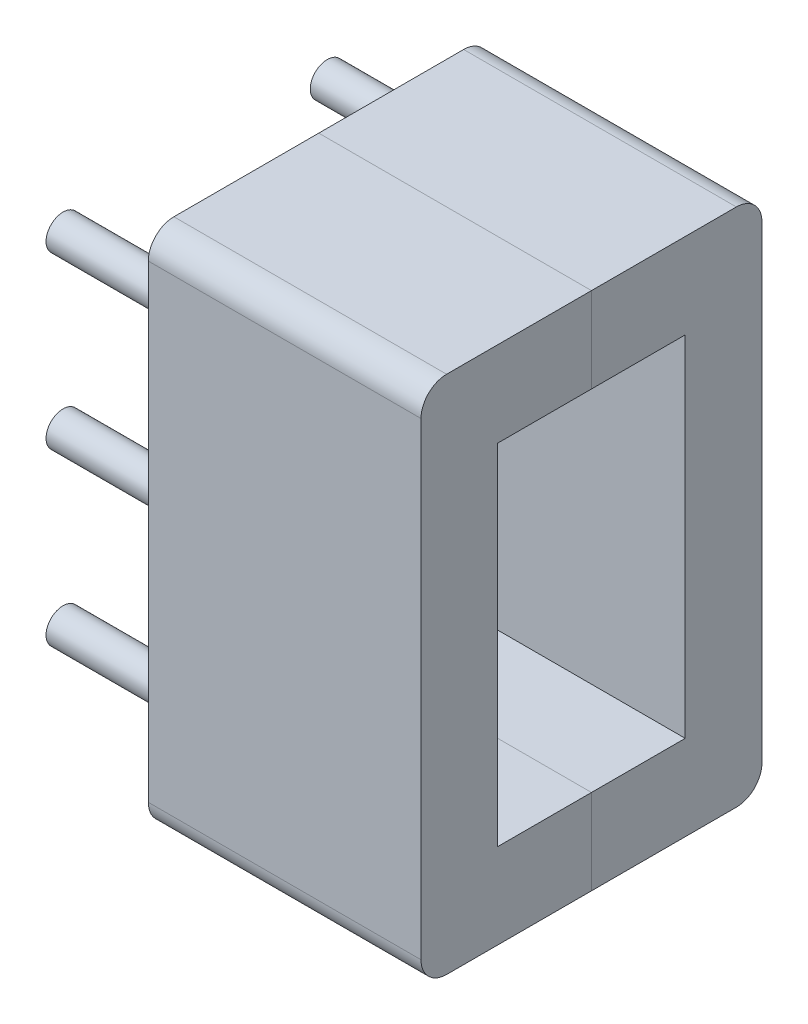
SolidWorks part; units mm, degrees
ref_plane "Alzado" through (0, 0, 0) normal (0, 0, 1) x (1, 0, 0)
ref_plane "Planta" through (0, 0, 0) normal (0, 1, 0) x (1, 0, 0)
ref_plane "Vista lateral" through (0, 0, 0) normal (1, 0, 0) x (0, 0, -1)
sketch "Croquis2" plane through (0, 0, 0) normal (1, 0, 0) x (0, 0, -1)
  line L0 (0, 24.489) -> (0, -53.3578) construction
  line L1 (5.835, 13.2874) -> (5.835, 12.9749) construction
  line L2 (10, 6.2874) -> (10, 3.7874) construction
  line L3 (5.835, -38.7126) -> (5.835, -38.4002) construction
  line L4 (5.835, -38.7126) -> (8, -38.7126) construction
  line L5 (9, -32.7126) -> (9, -37.7126) construction
  line L6 (10, -29.2126) -> (10, -31.7126) construction
  line L7 (5.835, 13.2874) -> (8, 13.2874) construction
  line L8 (9, 7.2874) -> (9, 12.2874) construction
  line L9 (6.5, 7.2874) -> (-6.5, 7.2874) construction
  line L10 (10, -29.2126) -> (10, 3.7874) construction
  line L11 (5.835, 13.2874) -> (5.835, 12.9749) construction
  line L12 (10, 6.2874) -> (10, 3.7874) construction
  line L13 (5.835, -38.7126) -> (5.835, -38.4002) construction
  line L14 (5.835, -38.7126) -> (8, -38.7126) construction
  line L15 (9, -32.7126) -> (9, -37.7126) construction
  line L16 (10, -29.2126) -> (10, -31.7126) construction
  line L17 (5.835, 13.2874) -> (8, 13.2874) construction
  line L18 (9, 7.2874) -> (9, 12.2874) construction
  line L19 (6.5, 7.2874) -> (-6.5, 7.2874) construction
  line L20 (10, -29.2126) -> (10, 3.7874) construction
  line L21 (-20, 17.7874) -> (20, 17.7874)
  line L22 (20, 17.7874) -> (20, -43.2126)
  line L24 (20, -43.2126) -> (-20, -43.2126)
  line L25 (-20, 17.7874) -> (-20, -43.2126)
  line L26 (-6.5, -32.7126) -> (6.5, -32.7126) construction
  line L27 (9, -32.7126) -> (6.5, -32.7126) construction
  line L28 (-6.5, -32.7126) -> (6.5, -32.7126) construction
  line L29 (9, -32.7126) -> (6.5, -32.7126) construction
  line L30 (-3, -33.7126) -> (-3, -32.7126) construction
  line L31 (3, -33.7126) -> (3, -32.7126) construction
  line L32 (-3, -33.7126) -> (-3, -32.7126) construction
  line L33 (3, -33.7126) -> (3, -32.7126) construction
  arc A0 (5.835, -38.4002) -> (4.335, -38.4002) centre (5.085, -36.3426) ccw construction
  arc A1 (4.335, 12.9749) -> (5.835, 12.9749) centre (5.085, 10.9174) ccw construction
  arc A2 (5.835, -38.4002) -> (4.335, -38.4002) centre (5.085, -36.3426) ccw construction
  arc A3 (4.335, 12.9749) -> (5.835, 12.9749) centre (5.085, 10.9174) ccw construction
  arc A4 (8, -38.7126) -> (9, -37.7126) centre (8, -37.7126) ccw construction
  arc A5 (9, -32.7126) -> (10, -31.7126) centre (9, -31.7126) ccw construction
  arc A6 (9, 12.2874) -> (8, 13.2874) centre (8, 12.2874) ccw construction
  arc A7 (10, 6.2874) -> (9, 7.2874) centre (9, 6.2874) ccw construction
  arc A8 (8, -38.7126) -> (9, -37.7126) centre (8, -37.7126) ccw construction
  arc A9 (9, -32.7126) -> (10, -31.7126) centre (9, -31.7126) ccw construction
  arc A10 (9, 12.2874) -> (8, 13.2874) centre (8, 12.2874) ccw construction
  arc A11 (10, 6.2874) -> (9, 7.2874) centre (9, 6.2874) ccw construction
  point P31 (0, -43.2126)
  point P33 (0, 17.7874)
  dimension "D1" = 4.5
  dimension "D2" = 10
  dimension "D3" = 4.5
extrude "Saliente-Extruir1" add sketch "Croquis2" against normal blind 32
sketch "Croquis4" plane through (0, 0, 0) normal (1, 0, 0) x (0, 0, -1)
  line L0 (3, -33.7126) -> (3, -32.7126) construction
  line L1 (-6.5, -32.7126) -> (6.5, -32.7126) construction
  line L2 (9, -32.7126) -> (6.5, -32.7126) construction
  line L3 (10, -29.2126) -> (10, -31.7126) construction
  line L4 (10, 6.2874) -> (10, 3.7874) construction
  line L5 (10, -29.2126) -> (10, 3.7874) construction
  line L6 (6.5, 7.2874) -> (-6.5, 7.2874) construction
  line L7 (0, 24.489) -> (0, -53.3578) construction
  line L8 (3, -33.7126) -> (3, -32.7126) construction
  line L9 (-6.5, -32.7126) -> (6.5, -32.7126) construction
  line L10 (9, -32.7126) -> (6.5, -32.7126) construction
  line L11 (10, -29.2126) -> (10, -31.7126) construction
  line L12 (10, 6.2874) -> (10, 3.7874) construction
  line L13 (10, -29.2126) -> (10, 3.7874) construction
  line L14 (6.5, 7.2874) -> (-6.5, 7.2874) construction
  line L15 (0, 24.489) -> (0, -53.3578) construction
  line L16 (-11, 7.7874) -> (11, 7.7874)
  line L17 (11, 7.7874) -> (11, -33.2126)
  line L19 (-11, 7.7874) -> (-11, -33.2126)
  line L35 (3, -33.7126) -> (2.5, -34.2126) construction
  line L43 (11, -33.2126) -> (-11, -33.2126)
  arc A0 (9, -32.7126) -> (10, -31.7126) centre (9, -31.7126) ccw construction
  arc A1 (9, -32.7126) -> (10, -31.7126) centre (9, -31.7126) ccw construction
  point P14 (0, -33.2126)
  point P20 (0, 7.7874)
  point P22 (0, -43.2126)
  dimension "D1" = 0.5
  dimension "D2" = 1
  dimension "D3" = 0.5
  dimension "D8" = 0.5
  dimension "D9" = 2.5
extrude "Cortar-Extruir1" cut sketch "Croquis4" against normal through all both and the other way through all
sketch "Croquis5" plane through (-32, 0, 0) normal (-1, 0, 0) x (0, 0, 1)
  line L0 (-9, 7.2874) -> (-9, 12.2874) construction
  line L1 (-9, -32.7126) -> (-9, -37.7126) construction
  line L2 (-5.835, -38.7126) -> (-8, -38.7126) construction
  line L3 (-5.835, 13.2874) -> (-8, 13.2874) construction
  line L4 (-9, 7.2874) -> (-9, 12.2874) construction
  line L5 (-9, -32.7126) -> (-9, -37.7126) construction
  line L6 (-5.835, -38.7126) -> (-8, -38.7126) construction
  line L7 (-5.835, 13.2874) -> (-8, 13.2874) construction
  line L8 (0, 24.489) -> (0, -53.3578) construction
  line L9 (0, 24.489) -> (0, -53.3578) construction
  line L10 (9.5, 13.7874) -> (-9.5, 13.7874)
  line L11 (-9.5, 13.7874) -> (-9.5, -39.2126)
  line L12 (-9.5, -39.2126) -> (9.5, -39.2126)
  line L13 (9.5, 13.7874) -> (9.5, -39.2126)
  arc A0 (-4.335, -38.4002) -> (-5.835, -38.4002) centre (-5.085, -36.3426) ccw construction
  arc A1 (-5.835, 12.9749) -> (-4.335, 12.9749) centre (-5.085, 10.9174) ccw construction
  arc A2 (-4.335, -38.4002) -> (-5.835, -38.4002) centre (-5.085, -36.3426) ccw construction
  arc A3 (-5.835, 12.9749) -> (-4.335, 12.9749) centre (-5.085, 10.9174) ccw construction
  point P21 (0, -39.2126)
  point P22 (0, 13.7874)
  dimension "D1" = 0.5
  dimension "D2" = 0.5
  dimension "D3" = 0.5
extrude "Cortar-Extruir2" cut sketch "Croquis5" against normal blind 8 and the other way through all
sketch "Croquis7" plane through (-24, 0, 0) normal (-1, 0, 0) x (0, 0, 1)
  line L4 (-9.5, 7.7874) -> (9.5, 7.7874)
  line L5 (9.5, 7.7874) -> (9.5, 13.7874)
  line L6 (9.5, 13.7874) -> (-9.5, 13.7874)
  line L7 (-9.5, 13.7874) -> (-9.5, 7.7874)
  line L8 (-9.5, 7.7874) -> (9.5, 7.7874)
  line L9 (9.5, 7.7874) -> (9.5, 13.7874)
  line L10 (9.5, 13.7874) -> (-9.5, 13.7874)
  line L11 (-9.5, 13.7874) -> (-9.5, 7.7874)
  line L12 (9.5, -33.2126) -> (-9.5, -33.2126)
  line L13 (-9.5, -33.2126) -> (-9.5, -39.2126)
  line L14 (-9.5, -39.2126) -> (9.5, -39.2126)
  line L15 (9.5, -39.2126) -> (9.5, -33.2126)
  line L16 (9.5, -33.2126) -> (-9.5, -33.2126)
  line L17 (-9.5, -33.2126) -> (-9.5, -39.2126)
  line L18 (-9.5, -39.2126) -> (9.5, -39.2126)
  line L19 (9.5, -39.2126) -> (9.5, -33.2126)
  dimension "D1" = 0
  dimension "D2" = 0
extrude "Saliente-Extruir2" add sketch "Croquis7" along normal up to surface (8 mm away) from offset 2.5 up to face at (-32, -12.7126, 0)
sketch "Croquis9" plane through (-32, 0, 0) normal (1, 0, 0) x (0, 0, -1)
  line L0 (-15.5, 3.7699) -> (-15.5, -40.0796) construction
  line L2 (100, 3.7699) -> (-100, 3.7699) construction
  line L3 (100, 12.7699) -> (-100, 12.7699) construction
  line L4 (-20, 17.7874) -> (-20, -43.2126) construction
  line L5 (-11, -33.2126) -> (-11, 7.7874) construction
  line L6 (-20, 17.7874) -> (-20, -43.2126) construction
  line L7 (-11, -33.2126) -> (-11, 7.7874) construction
  line L8 (0, 24.489) -> (0, -53.3578) construction
  line L9 (0, 24.489) -> (0, -53.3578) construction
  line L10 (-20, 6.2236) -> (-11, 6.2236) construction
  line L11 (-15.5, 3.7699) -> (-15.5, 12.7699) construction
  circle A0 centre (-15.5, 8.2699) radius 2
  circle A1 centre (-15.5, -31.7301) radius 2
  circle A2 centre (-15.5, -11.7301) radius 2
  circle A3 centre (15.5, -31.7301) radius 2
  circle A4 centre (15.5, -11.7301) radius 2
  circle A5 centre (15.5, 8.2699) radius 2
  point P14 (-15.5, 6.2236)
  dimension "D1" = 40
  dimension "D2" = 20
  dimension "D3" = 4
extrude "Saliente-Extruir3" add sketch "Croquis9" against normal blind 14.5
fillet "Redondeo1" radius 3 4 edges at (-16, -43.2126, 20) (-16, -43.2126, -20) (-16, 17.7874, -20) (-16, 17.7874, 20)
sketch "Croquis10" plane through (0, 0, 20) normal (0, 0, 1) x (1, 0, 0)
  line L0 (0, 14.7874) -> (-32, 14.7874) construction
  line L1 (0, 14.7874) -> (-32, 14.7874) construction
split "Partir1" trim tools "Alzado" bodies to split 108 resulting bodies 106 107
